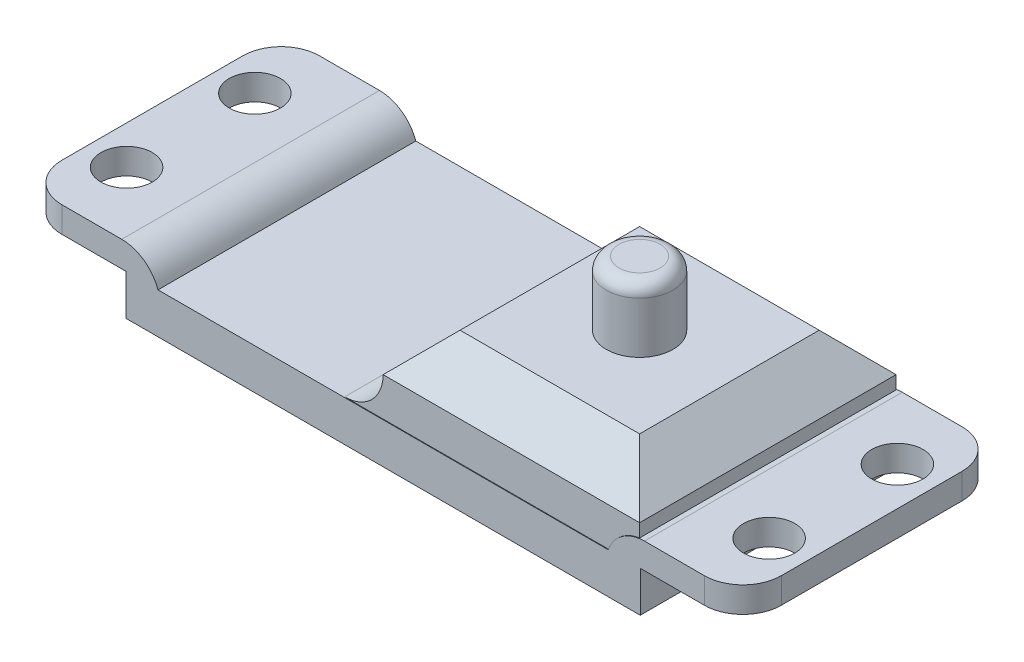
SolidWorks part; units mm, degrees
ref_plane "Front Plane" through (0, 0, 0) normal (0, 0, 1) x (1, 0, 0)
ref_plane "Top Plane" through (0, 0, 0) normal (0, 1, 0) x (1, 0, 0)
ref_plane "Right Plane" through (0, 0, 0) normal (1, 0, 0) x (0, 0, -1)
sketch "Sketch1" plane through (0, 0, 0) normal (0, 1, 0) x (1, 0, 0)
  line L1 (-20.05, -10.05) -> (20.05, -10.05)
  line L2 (-20.05, -10.05) -> (-20.05, 10.05)
  line L3 (-20.05, 10.05) -> (20.05, 10.05)
  line L4 (20.05, -10.05) -> (20.05, 10.05)
  line L5 (-20.05, -10.05) -> (20.05, 10.05) construction
  line L6 (-20.05, 10.05) -> (20.05, -10.05) construction
  point P0 (0, 0)
  dimension "D1" = 40.1
  dimension "D2" = 20.1
extrude "Boss-Extrude1" add sketch "Sketch1" along normal blind 3.175
sketch "Sketch2" plane through (0, 3.175, 0) normal (0, 1, 0) x (1, 0, 0)
  line L0 (-20.05, -10.05) -> (20.05, -10.05) construction
  line L1 (20.05, 10.05) -> (17.55, 10.05)
  line L2 (20.05, 10.05) -> (20.05, -10.05)
  line L3 (20.05, -10.05) -> (17.55, -10.05)
  line L4 (17.55, 10.05) -> (17.55, -10.05)
  dimension "D1" = 2.5
extrude "Boss-Extrude2" add sketch "Sketch2" along normal blind 2
sketch "Sketch3" plane through (20.05, 0, 0) normal (1, 0, 0) x (0, 0, -1)
  line L0 (10.05, 5.175) -> (10.05, 0) construction
  line L1 (-10.05, 5.175) -> (10.05, 5.175)
  line L2 (-10.05, 5.175) -> (-10.05, 3.175)
  line L3 (-10.05, 3.175) -> (10.05, 3.175)
  line L4 (10.05, 5.175) -> (10.05, 3.175)
  line L5 (10.05, 5.175) -> (10.05, 3.175) construction
extrude "Boss-Extrude3" add sketch "Sketch3" along normal blind 8
sketch "Sketch4" plane through (0, 3.175, 0) normal (0, -1, 0) x (1, 0, 0)
  line L0 (25.05, 5) -> (25.05, -5) construction
  line L1 (1.7463, 0) -> (-1.7463, 0) construction
  line L2 (20.05, 10.05) -> (20.05, -10.05) construction
  circle A0 centre (25.05, 5) radius 2
  circle A1 centre (25.05, -5) radius 2
  point P4 (25.05, 0)
  dimension "D1" = 4
  dimension "D2" = 10
  dimension "D3" = 5
extrude "Cut-Extrude1" cut sketch "Sketch4" against normal through all both and the other way through all
fillet "Fillet1" radius 3 1 edges at (17.55, 5.175, 0)
fillet "Fillet2" radius 3 2 edges at (28.05, 4.175, -10.05) (28.05, 4.175, 10.05)
mirror "Mirror2" about plane through (0, 0, 0) normal (1, 0, 0) of "Fillet2", "Fillet1", "Cut-Extrude1", "Boss-Extrude3", "Boss-Extrude2"
sketch "Sketch7" plane through (0, 3.175, 0) normal (0, 1, 0) x (1, 0, 0)
  line L1 (-0.05, 10) -> (19.95, 10)
  line L2 (-0.05, 10) -> (-0.05, -10)
  line L3 (-0.05, -10) -> (19.95, -10)
  line L4 (19.95, 10) -> (19.95, -10)
  line L5 (-0.05, 10) -> (19.95, -10) construction
  line L6 (-0.05, -10) -> (19.95, 10) construction
  circle A0 centre (25.05, -5) radius 2 construction
  point P0 (9.95, 0)
  dimension "D1" = 15.1
  dimension "D2" = 20
  dimension "D3" = 20
extrude "Boss-Extrude5" add sketch "Sketch7" along normal blind 6
sketch "Sketch5" plane through (0, 9.175, 0) normal (0, 1, 0) x (1, 0, 0)
  circle A0 centre (9.95, 0) radius 2.6
  circle A1 centre (25.05, -5) radius 2 construction
  dimension "D1" = 5.2
  dimension "D2" = 15.1
extrude "Boss-Extrude4" add sketch "Sketch5" along normal blind 5
fillet "Fillet4" radius 3 1 edges at (-0.05, 3.175, 0)
chamfer "Chamfer1" distance 3 angle 45 4 edges at (19.95, 9.175, 0) (9.95, 9.175, -10) (-0.05, 9.175, 0) (9.95, 9.175, 10)
fillet "Fillet5" radius 1 1 edges at (9.95, 14.175, 2.6)
